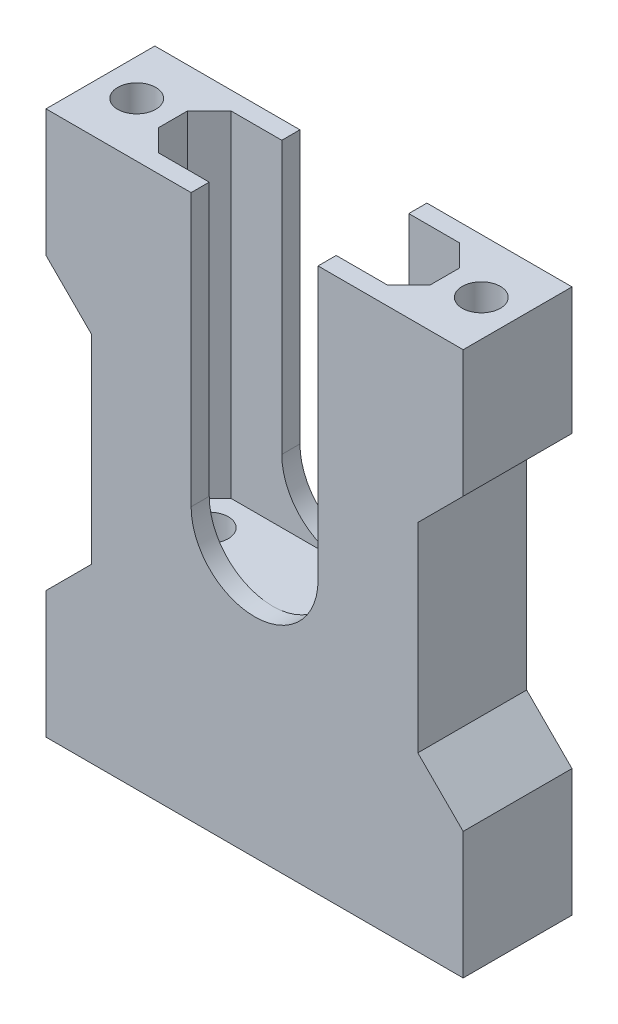
SolidWorks part; units mm, degrees
other "Uwaga1"
sketch "Szkic6" plane through (28, 56, 16) normal (0.3058, 0.389, 0.869) x (0.9408, -0.2636, -0.2131)
sketch "Szkic7" plane through (27, 56, 12) normal (0.3058, 0.389, 0.869) x (0.9408, -0.2636, -0.2131)
sketch "Szkic8" plane through (23, 56, 12) normal (0.3058, 0.389, 0.869) x (0.9408, -0.2636, -0.2131)
sketch "Szkic9" plane through (23, 56, 12) normal (0.3058, 0.389, 0.869) x (0.9408, -0.2636, -0.2131)
sketch "Szkic10" plane through (23, 56, 12) normal (0.3058, 0.389, 0.869) x (0.9408, -0.2636, -0.2131)
sketch "Szkic11" plane through (23, 70, 12) normal (0.3058, 0.389, 0.869) x (0.9408, -0.2636, -0.2131)
material "ABS"
ref_plane "Płaszczyzna przednia" through (0, 0, 0) normal (0, 0, 1) x (1, 0, 0)
ref_plane "Płaszczyzna górna" through (0, 0, 0) normal (0, 1, 0) x (1, 0, 0)
ref_plane "Płaszczyzna prawa" through (0, 0, 0) normal (1, 0, 0) x (0, 0, -1)
sketch "Szkic1" plane through (0, 0, 0) normal (0, 0, 1) x (1, 0, 0)
  line L0 (-23, 0) -> (23, 0)
  line L1 (23, 0) -> (23, 14)
  line L2 (23, 14) -> (18, 19)
  line L3 (18, 19) -> (18, 41)
  line L4 (18, 41) -> (23, 46)
  line L5 (23, 46) -> (23, 60)
  line L7 (-23, 60) -> (-23, 46)
  line L8 (-23, 46) -> (-18, 41)
  line L9 (-18, 41) -> (-18, 19)
  line L10 (-18, 19) -> (-23, 14)
  line L11 (-23, 14) -> (-23, 0)
  line L12 (23, 60) -> (7, 60)
  line L14 (-23, 60) -> (-7, 60)
  line L16 (7, 30) -> (7, 60)
  line L17 (-18, 30) -> (18, 30) construction
  line L18 (-7, 30) -> (-7, 60)
  arc A0 (-7, 30) -> (7, 30) centre (0, 30) ccw
  point P4 (0, 0)
  dimension "D2" = 5
  dimension "D3" = 5
  dimension "D4" = 5
  dimension "D5" = 5
  dimension "D6" = 135
  dimension "D7" = 60
  dimension "D8" = 180
  dimension "D9" = 14
  dimension "D10" = 14
  dimension "D11" = 14
  dimension "D12" = 14
  dimension "D13" = 14
  dimension "D14" = 46
  dimension "D15" = 16
  dimension "D16" = 16
  dimension "D17" = 60
extrude "Dodanie-wyciągnięcie1" add sketch "Szkic1" along normal blind 12
ref_plane "Płaszczyzna1" through (0, 60, 0) normal (0, 1, 0) x (1, 0, 0)
sketch "Szkic2" plane through (0, 60, 0) normal (0, 1, 0) x (1, 0, 0)
  line L0 (0, 0) -> (0, -6) construction
  line L1 (0, -6) -> (-19, -6) construction
  line L2 (0, -6) -> (19, -6) construction
  circle A0 centre (-19, -6) radius 2.1
  circle A1 centre (19, -6) radius 2.1
  dimension "D3" = 4.2
  dimension "D5" = 4.2
  dimension "D1" = 6
  dimension "D2" = 19
  dimension "D4" = 19
extrude "Wytnij-wyciągnięcie1" cut sketch "Szkic2" against normal blind 10
ref_plane "Płaszczyzna2" through (0, 30, 0) normal (0, -1, 0) x (-1, 0, 0)
mirror "Lustro1" about plane through (0, 30, 0) normal (0, -1, 0) of "Wytnij-wyciągnięcie1"
sketch "Szkic3" plane through (0, 60, 0) normal (0, -1, 0) x (-1, 0, 0)
  line L0 (0, 0) -> (0, -6) construction
  line L1 (0, -6) -> (15, -6) construction
  line L2 (15, -10) -> (15, -2) construction
  line L6 (15, -2) -> (12.6, -2) construction
  line L7 (15, -2) -> (15, -4.4) construction
  line L8 (12.6, -2) -> (-12.6, -2)
  line L9 (15, -4.4) -> (12.6, -2)
  line L10 (15, -4.4) -> (15, -7.6)
  line L11 (-15, -4.4) -> (-15, -7.6)
  line L12 (-15, -4.4) -> (-12.6, -2)
  line L13 (-15, -7.6) -> (-12.6, -10)
  line L14 (12.6, -10) -> (-12.6, -10)
  line L15 (15, -7.6) -> (12.6, -10)
  point P7 (15, -6)
  point P13 (0, -2)
  point P14 (-15, -6)
  dimension "D1" = 6
  dimension "D2" = 15
  dimension "D3" = 8
  dimension "D4" = 2.4
  dimension "D5" = 2.4
extrude "Wytnij-wyciągnięcie2" cut sketch "Szkic3" along normal blind 37
sketch "Szkic4" plane through (0, 23, 0) normal (0, 1, 0) x (1, 0, 0)
  line L0 (0, 0) -> (0, -6) construction
  line L1 (-11, -6) -> (11, -6) construction
  circle A0 centre (11, -6) radius 2.1
  circle A1 centre (-11, -6) radius 2.1
  dimension "D3" = 4.2
  dimension "D1" = 6
  dimension "D2" = 11
extrude "Wytnij-wyciągnięcie3" cut sketch "Szkic4" against normal up to next
sketch "Szkic5" plane through (0, 0, 0) normal (0, -1, 0) x (1, 0, 0)
  line L0 (0, -6.6) -> (0, 6.6) construction
  line L1 (11, 1.7276) -> (14.7, 3.8638)
  line L2 (14.7, 3.8638) -> (14.7, 8.1362)
  line L3 (14.7, 8.1362) -> (11, 10.2724)
  line L4 (11, 10.2724) -> (7.3, 8.1362)
  line L5 (7.3, 8.1362) -> (7.3, 3.8638)
  line L6 (7.3, 3.8638) -> (11, 1.7276)
  line L7 (-7.3, 3.8638) -> (-11, 1.7276)
  line L8 (-7.3, 8.1362) -> (-7.3, 3.8638)
  line L9 (-11, 10.2724) -> (-7.3, 8.1362)
  line L10 (-14.7, 8.1362) -> (-11, 10.2724)
  line L11 (-14.7, 3.8638) -> (-14.7, 8.1362)
  line L12 (-11, 1.7276) -> (-14.7, 3.8638)
  circle A0 centre (11, 6) radius 3.7 construction
  circle A1 centre (-11, 6) radius 3.7 construction
  dimension "D1" = 7.4
extrude "Wytnij-wyciągnięcie4" cut sketch "Szkic5" against normal blind 6
equation "\"hight\" = 60"
equation "\"D10@Szkic1\"=\"InsertHight\""
equation "\"InsertHight\"=14"
equation "\"D9@Szkic1\"=\"InsertHight\""
equation "\"D11@Szkic1\"=\"InsertHight\""
equation "\"D12@Szkic1\"=\"InsertHight\""
equation "\"FazeX\"= 5"
equation "\"D5@Szkic1\"=\"FazeX\""
equation "\"D4@Szkic1\"=\"FazeX\""
equation "\"D2@Szkic1\"=\"FazeX\""
equation "\"D3@Szkic1\"=\"FazeX\""
equation "\"width\"= 46"
equation "\"D15@Szkic1\"=\"TopWidth\""
equation "\"TopWidth\"= 16"
equation "\"D16@Szkic1\"=\"TopWidth\""
equation "\"D7@Szkic1\"=\"hight\""
equation "\"D17@Szkic1\"=\"hight\""
equation "\"depth\"= 12"
equation "\"D1@Szkic2\"=\"depth\"/2"
equation "\"D1@Dodanie-wyciągnięcie1\"=\"depth\""
equation "\"D14@Szkic1\"=\"width\""
equation "\"ToInsertX\"= ( \"width\" - \"TopWidth\" - \"TopWidth\" ) / 2 + ( \"TopWidth\" / 2 ) + \"FazeX\" * 0.8"
equation "\"InsertDiameter\"= 4.2"
equation "\"D3@Szkic2\"=\"InsertDiameter\""
equation "\"D2@Szkic2\"=\"ToInsertX\""
equation "\"D4@Szkic2\"=\"ToInsertX\""
equation "\"D5@Szkic2\"=\"InsertDiameter\""
equation "\"InsertDepth\"=10"
equation "\"D1@Wytnij-wyciągnięcie1\"=\"InsertDepth\""
equation "\"Diameter\"= \"width\" - \"TopWidth\" - \"TopWidth\""
equation "\"D1@Szkic3\"=\"depth\"/2"
equation "\"RailX\"= 8"
equation "\"D2@Szkic3\"=\"Diameter\"/2+\"RailX\""
equation "\"RailZ\"= 8"
equation "\"D3@Szkic3\"=\"RailZ\""
equation "\"D1@Wytnij-wyciągnięcie2\"=\"hight\"/2+\"Diameter\"/2"
equation "\"D4@Szkic3\" = \"RailZ\" * 0.3"
equation "\"D5@Szkic3\" = \"RailZ\" * 0.3"
equation "\"D1@Szkic4\"=\"depth\"/2"
equation "\"D2@Szkic4\"=\"Diameter\"/2+\"RailX\"/2"
